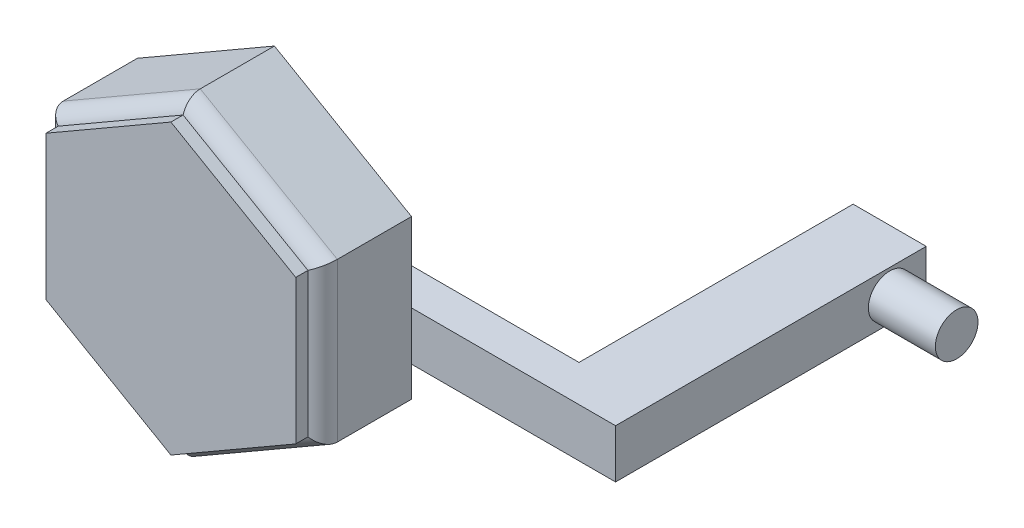
SolidWorks part; units mm, degrees
ref_plane "Ön Düzlem" through (0, 0, 0) normal (0, 0, 1) x (1, 0, 0)
ref_plane "Üst Düzlem" through (0, 0, 0) normal (0, 1, 0) x (1, 0, 0)
ref_plane "Sağ Düzlem" through (0, 0, 0) normal (1, 0, 0) x (0, 0, -1)
sketch "Sketch1" plane through (0, 0, 0) normal (0, 0, 1) x (1, 0, 0)
  line L0 (0, -25.9808) -> (0, 25.9808) construction
  line L1 (0, 25.9808) -> (-22.5, 12.9904)
  line L2 (-22.5, 12.9904) -> (-22.5, -12.9904)
  line L3 (-22.5, -12.9904) -> (0, -25.9808)
  line L4 (0, -25.9808) -> (22.5, -12.9904)
  line L5 (22.5, -12.9904) -> (22.5, 12.9904)
  line L6 (22.5, 12.9904) -> (0, 25.9808)
  circle A0 centre (0, 0) radius 22.5 construction
  dimension "D1" = 45
extrude "Boss-Extrude1" add sketch "Sketch1" along normal blind 15
sketch "Sketch2" plane through (0, 0, 15) normal (0, 0, 1) x (1, 0, 0)
  line L12 (20.5, 11.8357) -> (0, 23.6714)
  line L13 (0, 23.6714) -> (-20.5, 11.8357)
  line L14 (-20.5, 11.8357) -> (-20.5, -11.8357)
  line L15 (-20.5, -11.8357) -> (0, -23.6714)
  line L16 (0, -23.6714) -> (20.5, -11.8357)
  line L17 (20.5, -11.8357) -> (20.5, 11.8357)
  line L18 (20.5, 11.8357) -> (0, 23.6714)
  line L19 (0, 23.6714) -> (-20.5, 11.8357)
  line L20 (-20.5, 11.8357) -> (-20.5, -11.8357)
  line L21 (-20.5, -11.8357) -> (0, -23.6714)
  line L22 (0, -23.6714) -> (20.5, -11.8357)
  line L23 (20.5, -11.8357) -> (20.5, 11.8357)
  dimension "D1" = 2
extrude "Boss-Extrude2" add sketch "Sketch2" along normal blind 2
fillet "Fillet1" radius 3 6 edges at (-11.25, 19.4856, 15) (-22.5, 0, 15) (-11.25, -19.4856, 15) (11.25, -19.4856, 15) (22.5, 0, 15) (11.25, 19.4856, 15)
sketch "Sketch3" plane through (0, 0, 0) normal (0, 0, -1) x (-1, 0, 0)
  line L1 (0, 0) -> (-56, 0)
  line L2 (0, 0) -> (0, -8)
  line L3 (0, -8) -> (-56, -8)
  line L4 (-56, 0) -> (-56, -8)
  dimension "D1" = 56
  dimension "D2" = 8
extrude "Boss-Extrude3" add sketch "Sketch3" along normal blind 6
sketch "Sketch4" plane through (0, 0, -6) normal (0, 0, -1) x (-1, 0, 0)
  line L0 (0, 0) -> (-56, 0) construction
  line L1 (-44, 0) -> (-56, 0)
  line L2 (-44, 0) -> (-44, -8)
  line L3 (-44, -8) -> (-56, -8)
  line L4 (-56, 0) -> (-56, -8)
  dimension "D1" = 12
extrude "Boss-Extrude4" add sketch "Sketch4" along normal blind 45
sketch "Sketch5" plane through (56, 0, 0) normal (1, 0, 0) x (0, 0, -1)
  line L0 (51, 0) -> (51, -8) construction
  line L1 (51, 0) -> (0, 0) construction
  circle A0 centre (45, -4) radius 3.5
  dimension "D1" = 6
  dimension "D2" = 7
  dimension "D3" = 4
extrude "Boss-Extrude5" add sketch "Sketch5" along normal blind 11
fillet "Fillet2" radius 4 1 edges at (0, -4, -6)
